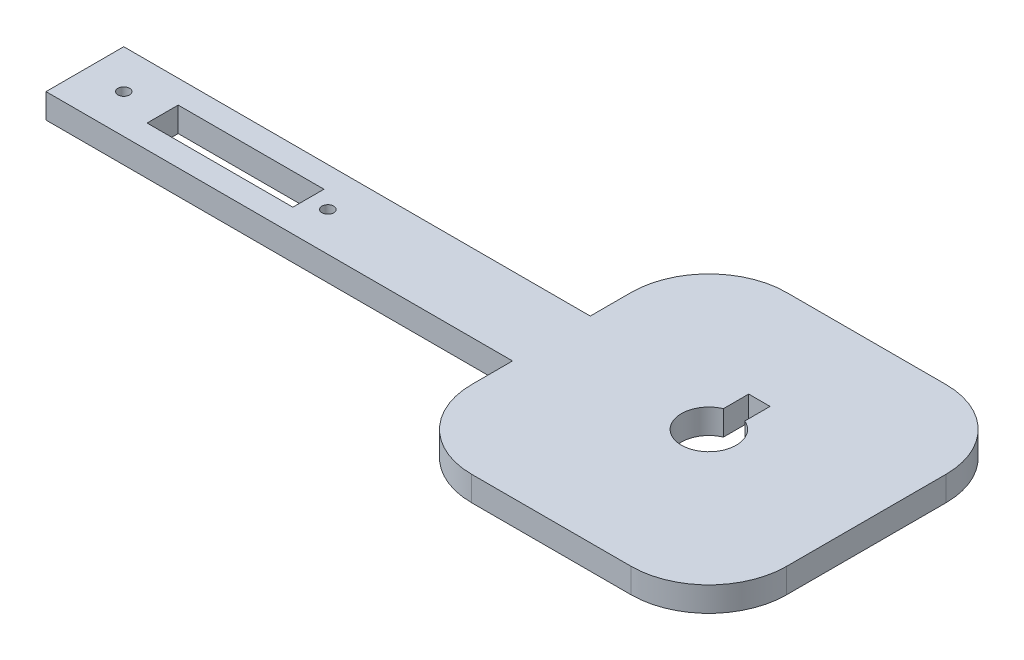
SolidWorks part; units mm, degrees
ref_plane "Front Plane" through (0, 0, 0) normal (0, 0, 1) x (1, 0, 0)
ref_plane "Top Plane" through (0, 0, 0) normal (0, 1, 0) x (1, 0, 0)
ref_plane "Right Plane" through (0, 0, 0) normal (1, 0, 0) x (0, 0, -1)
sketch "Sketch1" plane through (0, 0, 0) normal (0, 1, 0) x (1, 0, 0)
  line L0 (-40.5, 0) -> (-140.5, 0) construction
  line L1 (-40.5, 40.5) -> (40.5, 40.5)
  line L2 (-40.5, 40.5) -> (-40.5, 10)
  line L3 (-40.5, -40.5) -> (40.5, -40.5)
  line L4 (40.5, 40.5) -> (40.5, -40.5)
  line L5 (-40.5, 40.5) -> (40.5, -40.5) construction
  line L6 (-40.5, -40.5) -> (40.5, 40.5) construction
  line L7 (-40.5, -10) -> (-140.5, -10)
  line L8 (-40.5, 10) -> (-140.5, 10)
  line L9 (-40.5, 0) -> (0, 0) construction
  line L10 (-140.5, 0) -> (-65.5, 0) construction
  line L11 (-140.5, 4) -> (-65.5, 4) construction
  line L12 (-140.5, -4) -> (-65.5, -4) construction
  line L13 (-40.5, -10) -> (-40.5, -40.5)
  line L14 (-40.5, 10) -> (-40.5, -10) construction
  line L15 (-140.5, 10) -> (-140.5, -10) construction
  line L16 (-150.5, 0) -> (-140.5, 0) construction
  line L17 (-2.75, 6.4915) -> (-2.75, 13)
  line L18 (-2.75, 13) -> (2.75, 13)
  line L19 (2.75, 13) -> (2.75, 6.4915)
  line L20 (0, 0) -> (0, 13) construction
  line L21 (0, 32.5) -> (0, 0) construction
  line L22 (0, 0) -> (32.5, 0) construction
  line L23 (-140.5, 4) -> (-140.5, -4)
  line L24 (0, -32.5) -> (0, 0) construction
  line L25 (-140.5, -4) -> (-103, -4)
  line L26 (-103, -4) -> (-103, 4)
  line L27 (-103, 4) -> (-140.5, 4)
  line L28 (-140.5, 10) -> (-160.5, 10)
  line L29 (-160.5, 10) -> (-160.5, -10)
  line L30 (-160.5, -10) -> (-140.5, -10)
  arc A0 (-2.75, 6.4915) -> (2.75, 6.4915) centre (0, 0) ccw
  circle A1 centre (0, 0) radius 32.5 construction
  arc A7 (-140.5, 10) -> (-140.5, -10) centre (-140.5, 0) ccw construction
  arc A8 (-140.5, 4) -> (-140.5, -4) centre (-140.5, 0) ccw construction
  arc A9 (-65.5, -4) -> (-65.5, 4) centre (-65.5, 0) ccw construction
  circle A10 centre (-98, 0) radius 1.5
  circle A11 centre (-150.5, 0) radius 1.5
  point P17 (-90.5, 0)
  point P26 (-103, 0)
  point P40 (-160.5, 0)
  dimension "D1" = 14.1
  dimension "D2" = 65
  dimension "D5" = 20
  dimension "D11" = 13
  dimension "D12" = 3
  dimension "D15" = 3
  dimension "D3" = 81
  dimension "D4" = 81
  dimension "D6" = 100
  dimension "D7" = 20
  dimension "D8" = 75
  dimension "D9" = 8
  dimension "D10" = 5.5
  dimension "D13" = 10
  dimension "D14" = 5
extrude "Boss-Extrude1" add sketch "Sketch1" along normal blind 6.35
fillet "Fillet1" radius 20 4 edges at (-40.5, 3.175, -40.5) (40.5, 3.175, -40.5) (40.5, 3.175, 40.5) (-40.5, 3.175, 40.5)
